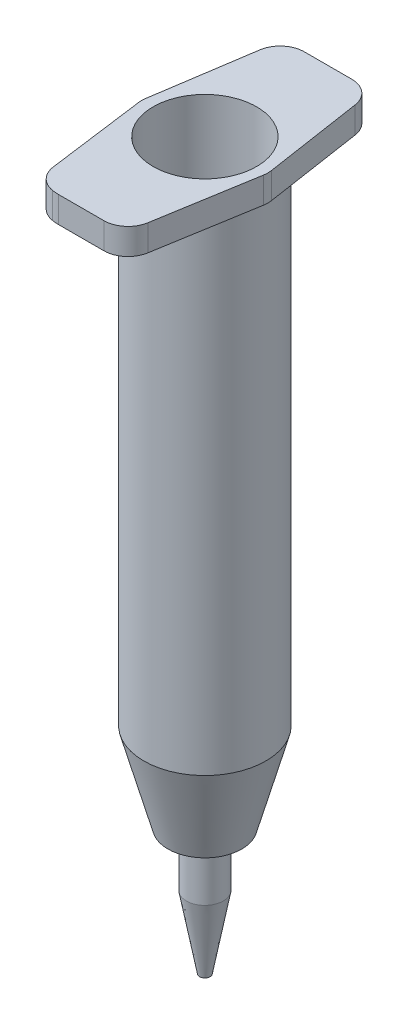
SolidWorks part; units mm, degrees
ref_plane "Front Plane" through (0, 0, 0) normal (0, 0, 1) x (1, 0, 0)
ref_plane "Top Plane" through (0, 0, 0) normal (0, 1, 0) x (1, 0, 0)
ref_plane "Right Plane" through (0, 0, 0) normal (1, 0, 0) x (0, 0, -1)
sketch "Sketch1" plane through (0, 0, 0) normal (0, 1, 0) x (1, 0, 0)
  circle A0 centre (0, 0) radius 7.6
  dimension "D1" = 15.2
extrude "Boss-Extrude1" add sketch "Sketch1" along normal blind 71.3
chamfer "Chamfer1" distance 3 distance2 11 1 edges at (0, 0, 7.6) first distance on face at (0, 0, 7.6)
sketch "Sketch2" plane through (0, 0, 0) normal (0, -1, 0) x (1, 0, 0)
  circle A0 centre (0, 0) radius 2.3
  dimension "D1" = 4.6
extrude "Boss-Extrude2" add sketch "Sketch2" along normal blind 15.75
chamfer "Chamfer2" distance 9 distance2 1.65 1 edges at (0, -15.75, -2.3) first distance on face at (0, -15.75, -2.3)
sketch "Sketch3" plane through (0, 71.3, 0) normal (0, 1, 0) x (1, 0, 0)
  line L1 (7.875, 15.35) -> (-7.875, 15.35)
  line L2 (7.875, 15.35) -> (7.875, -15.35)
  line L3 (7.875, -15.35) -> (-7.875, -15.35)
  line L4 (-7.875, 15.35) -> (-7.875, -15.35)
  dimension "D1" = 15.75
  dimension "D2" = 30.7
  dimension "D3" = 7.875
  dimension "D4" = 15.35
extrude "Boss-Extrude3" add sketch "Sketch3" along normal blind 3.25
fillet "Fillet1" radius 5 4 edges at (-7.875, 72.925, 15.35) (7.875, 72.925, 15.35) (-7.875, 72.925, -15.35) (7.875, 72.925, -15.35)
sketch "Sketch4" plane through (0, 74.55, 0) normal (0, 1, 0) x (1, 0, 0)
  circle A0 centre (0, 0) radius 6.45
  dimension "D1" = 12.9
extrude "Cut-Extrude1" cut sketch "Sketch4" against normal blind 63.5
sketch "Sketch5" plane through (0, 74.55, 0) normal (0, 1, 0) x (1, 0, 0)
  line L0 (5.6686, 14.4968) -> (7.875, 0)
  line L1 (7.875, -10.35) -> (7.875, 10.35) construction
  line L2 (-5.6814, 14.4881) -> (-7.875, 0)
  line L3 (-7.875, 10.35) -> (-7.875, -10.35) construction
  line L4 (5.4336, -14.6458) -> (7.875, 0)
  line L5 (-5.9653, -14.2807) -> (-7.875, 0)
  line L7 (7.875, 0) -> (7.875, 10.35)
  line L8 (-7.875, 0) -> (-7.875, -10.35)
  line L11 (-7.875, 10.35) -> (-7.875, -10.35)
  line L12 (-2.875, -15.35) -> (2.875, -15.35)
  line L13 (-7.875, 10.35) -> (-7.875, -10.35)
  line L14 (2.875, 15.35) -> (-2.875, 15.35)
  line L21 (7.875, -10.35) -> (7.875, 10.35)
  line L22 (7.875, -10.35) -> (7.875, 10.35)
  arc A0 (7.875, 10.35) -> (2.875, 15.35) centre (2.875, 10.35) ccw construction
  arc A1 (-2.875, 15.35) -> (-7.875, 10.35) centre (-2.875, 10.35) ccw construction
  arc A2 (2.875, -15.35) -> (7.875, -10.35) centre (2.875, -10.35) ccw construction
  arc A7 (-7.875, -10.35) -> (-2.875, -15.35) centre (-2.875, -10.35) ccw
  arc A8 (2.875, -15.35) -> (7.875, -10.35) centre (2.875, -10.35) ccw
  arc A9 (7.875, 10.35) -> (2.875, 15.35) centre (2.875, 10.35) ccw
  arc A10 (-2.875, 15.35) -> (-7.875, 10.35) centre (-2.875, 10.35) ccw
  arc A11 (-7.875, -10.35) -> (-5.9653, -14.2807) centre (-2.875, -10.35) ccw
  arc A13 (7.875, 10.35) -> (5.6686, 14.4968) centre (2.875, 10.35) ccw
  arc A14 (-5.6814, 14.4881) -> (-7.875, 10.35) centre (-2.875, 10.35) ccw
  arc A15 (2.875, -15.35) -> (7.875, -10.35) centre (2.875, -10.35) ccw
  point P14 (7.875, -0.5216)
  point P16 (-5.6686, 14.4968)
  point P18 (3.9634, 15.2301)
  point P24 (4.7564, -14.9825)
  point P28 (-5.9164, -14.6458)
  point P36 (7.875, 0)
  point P41 (-7.875, 0)
  point P42 (-7.8235, 0.3403)
  line M10 (-7.875, 10.35) -> (-7.875, -10.35)
  arc M11 (-7.875, -10.35) -> (-2.875, -15.35) centre (-2.875, -10.35) ccw
  arc M13 (2.875, -15.35) -> (7.875, -10.35) centre (2.875, -10.35) ccw
  line M14 (7.875, -10.35) -> (7.875, 10.35)
  arc M15 (7.875, 10.35) -> (2.875, 15.35) centre (2.875, 10.35) ccw
  arc M17 (-2.875, 15.35) -> (-7.875, 10.35) centre (-2.875, 10.35) ccw
  dimension "D1" = 11.35
  dimension "D3" = 0
extrude "Cut-Extrude2" cut sketch "Sketch5" against normal blind 63.5 contours L5 M11 M10 | L4 M13 M14 | L0 M15 M14 | L2 M17 M10 region at (7.1172, 74.55, -8.8772) region at (7.0349, 74.55, 8.9642) region at (-7.1217, 74.55, -8.8722) region at (-7.2206, 74.55, 8.7564)
fillet "Fillet2" radius 3 6 edges at (-5.6814, 72.925, -14.4881) (-5.9653, 72.925, 14.2807) (5.4336, 72.925, 14.6458) (5.6686, 72.925, -14.4968) (7.875, 72.925, 0) (-7.875, 72.925, 0)
sketch "Sketch7" plane through (0, 11.05, 0) normal (0, 1, 0) x (1, 0, 0)
  circle A1 centre (0, 0) radius 6.45
  circle A2 centre (0, 0) radius 6.45
  dimension "D1" = 0
ref_axis "Axis1" through (0, 11, 0) along (0, -1, 0)
sketch "Sketch8" plane through (0, 11.05, 0) normal (0, 1, 0) x (1, 0, 0)
  line L0 (0, 0) -> (8.9782, 0) construction
  circle A3 centre (0, 0) radius 6.45
  circle A4 centre (0, 0) radius 6.45
  dimension "D1" = 0
sketch "Sketch9" plane through (0, 0, 0) normal (0, -1, 0) x (1, 0, 0)
  line L0 (0, 0) -> (8.6551, 0)
ref_point "Point1"
ref_point "Point4" parameters "D1"=3.6
ref_axis "Axis2" through (6.45, 11.05, 0) along (-0.2497, -0.9683, 0)
ref_plane "Plane1" through (0, 1, 0) normal (0, -1, 0) x (-1, 0, 0)
sketch "Sketch10" plane through (0, 1, 0) normal (0, -1, 0) x (1, 0, 0)
  circle A0 centre (0, 0) radius 3.6
loft "Cut-Loft1" cut profiles "Sketch7", "Sketch10" connector at (6.2774, 11.05, 1.4821) connector at (3.134, 1, 1.7714)
sketch "Sketch11" plane through (0, 1, 0) normal (0, 1, 0) x (1, 0, 0)
  circle A0 centre (0, 0) radius 1.27
  dimension "D1" = 2.54
sketch "Sketch12" plane through (0, -15.75, 0) normal (0, -1, 0) x (1, 0, 0)
  circle A0 centre (0, 0) radius 0.25
  dimension "D1" = 0.5
loft "Cut-Loft2" cut profiles "Sketch12", "Sketch11" connector at (0.1603, -15.75, -0.1918) connector at (0.1044, 1, -1.2657)
equation "\"D3@Sketch3\"=\"D1@Sketch3\"/2"
equation "\"D4@Sketch3\"=\"D2@Sketch3\"/2"
